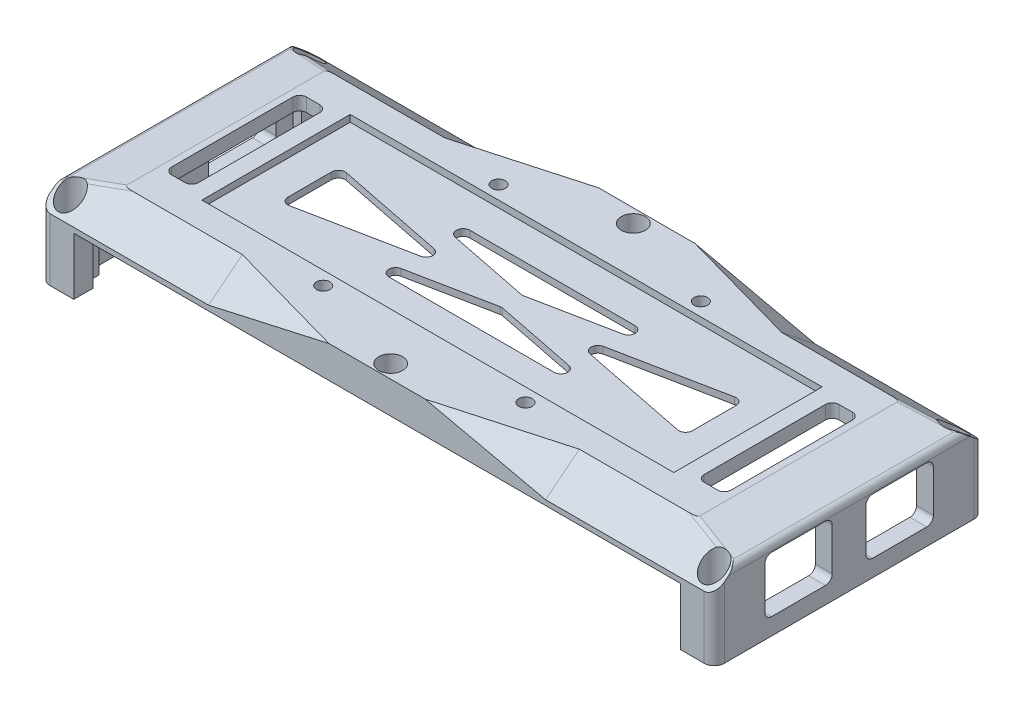
SolidWorks part; units mm, degrees
material "ABS"
ref_plane "前基準面" through (0, 0, 0) normal (0, 0, 1) x (1, 0, 0)
ref_plane "上基準面" through (0, 0, 0) normal (0, 1, 0) x (1, 0, 0)
ref_plane "右基準面" through (0, 0, 0) normal (1, 0, 0) x (0, 0, -1)
sketch "草圖1" plane through (0, 0, 0) normal (0, 1, 0) x (1, 0, 0)
  line L1 (-100, -40) -> (100, -40)
  line L2 (-100, -40) -> (-100, 40)
  line L3 (-100, 40) -> (100, 40)
  line L4 (100, -40) -> (100, -20)
  line L5 (-100, -40) -> (100, 40) construction
  line L6 (-100, 40) -> (100, -40) construction
  line L10 (-1000, 0) -> (49000, 0) construction
  line L17 (-85, 40) -> (-100, 40)
  line L18 (-100, 25) -> (-100, 40)
  line L19 (0, -1000) -> (0, 49000) construction
  line L23 (85, 40) -> (100, 40)
  line L24 (100, 25) -> (100, 40)
  line L29 (100, -25) -> (100, -40)
  line L30 (85, -40) -> (100, -40)
  line L35 (-85, -40) -> (-100, -40)
  line L36 (-100, -25) -> (-100, -40)
  line L40 (100, 0) -> (100, 40)
  line L48 (100, 0) -> (100, -20)
  line L50 (-90, 30) -> (90, 30)
  line L51 (-90, 30) -> (-90, -30)
  line L52 (-90, -30) -> (90, -30)
  line L53 (90, 30) -> (90, -30)
  point P0 (0, 0)
  dimension "D2" = 200
  dimension "D3" = 80
  dimension "D4" = 10
  dimension "D1" = 10
extrude "填料-伸長2" add sketch "草圖1" along normal blind 2 contours L1 L4 L3 L2 L18 L17 L24 L23 L30 L29 L36 L35 region at (-97.8459, 0, 32.5)
sketch "草圖7" plane through (0, 0, 0) normal (0, -1, 0) x (1, 0, 0)
  line L0 (-1000, 0) -> (-95, 0) construction
  line L1 (0, -1010) -> (0, 48990) construction
  line L3 (-30, -30) -> (30, -30)
  line L16 (0, 0) -> (49000, 0) construction
  line L18 (-100, 40) -> (-30, 40)
  line L19 (-100, 40) -> (-100, -40)
  line L20 (-100, -40) -> (-30, -40)
  line L21 (100, 40) -> (100, -40)
  line L22 (-90, 30) -> (-30, 30)
  line L23 (-90, 30) -> (-90, -30)
  line L24 (-90, -30) -> (-30, -30)
  line L25 (90, 30) -> (90, -30)
  line L33 (-30, 40) -> (30, 40)
  line L34 (-30, 30) -> (30, 30)
  line L35 (-30, -40) -> (30, -40)
  line L36 (30, -30) -> (90, -30)
  line L37 (30, -40) -> (100, -40)
  line L38 (30, 40) -> (100, 40)
  line L39 (30, 30) -> (90, 30)
  dimension "D1" = 180
  dimension "D2" = 10
  dimension "D4" = 10
  dimension "D6" = 60
extrude "填料-伸長5" add sketch "草圖7" along normal blind 3.5
sketch "草圖8" plane through (0, 2, 0) normal (0, 1, 0) x (1, 0, 0)
  line L1 (-100, 40) -> (100, 40)
  line L2 (-100, 40) -> (-100, -40)
  line L3 (-100, -40) -> (100, -40)
  line L4 (100, 40) -> (100, -40)
extrude "填料-伸長6" add sketch "草圖8" along normal blind 4
chamfer "導角4" distance 3 distance2 15 2 edges at (-100, 6, 0) (100, 6, 0) first distance on face at (-100, 1.25, 0) first distance on face at (100, 1.25, 0)
sketch "草圖10" plane through (0, -3.5, 0) normal (0, -1, 0) x (1, 0, 0)
  line L0 (-100, -40) -> (100, -40) construction
  line L1 (-100, 40) -> (-90, 40)
  line L2 (-100, 40) -> (-100, -40)
  line L3 (-100, -40) -> (-90, -40)
  line L4 (-90, 40) -> (-90, -40)
  line L5 (0, 0) -> (0, 67.9588) construction
  line L6 (0, 0) -> (59.8785, 0) construction
  line L7 (100, -40) -> (90, -40)
  line L8 (90, 40) -> (90, -40)
  line L9 (100, 40) -> (90, 40)
  line L10 (100, 40) -> (100, -40)
  line L11 (-100, 40) -> (-100, -40) construction
  dimension "D2" = 10
extrude "填料-伸長7" add sketch "草圖10" along normal blind 17
sketch "草圖9" plane through (0, 0, 0) normal (0, 1, 0) x (1, 0, 0)
  line L0 (-1000, 0) -> (49000, 0) construction
  line L1 (0, -994.7968) -> (0, 49005.2032) construction
  line L2 (85, 40) -> (-85, 40) construction
  line L4 (100, -40) -> (100, 40) construction
  circle A0 centre (95.5, 35.5) radius 2
  circle A1 centre (-95.5, 35.5) radius 2
  circle A2 centre (-95.5, -35.5) radius 2
  circle A3 centre (95.5, -35.5) radius 2
  circle A4 centre (0, 36) radius 2
  circle A5 centre (0, -36) radius 2
  circle A6 centre (30, 26) radius 2
  circle A7 centre (-30, 26) radius 2
  circle A8 centre (30, -26) radius 2
  circle A9 centre (-30, -26) radius 2
  dimension "D1" = 4
  dimension "D4" = 4
  dimension "D5" = 4
  dimension "D2" = 4.5
  dimension "D3" = 4.5
  dimension "D6" = 30
  dimension "D7" = 26
  dimension "D8" = 4
extrude "除料-伸長1" cut sketch "草圖9" against normal through all and the other way through all contours A5 | A4 | A1 | A2 | A0 | A3
sketch "草圖11" plane through (0, 6, 0) normal (0, 1, 0) x (1, 0, 0)
  line L0 (0.0013, 21.2615) -> (0.0013, 0) construction
  line L1 (0.0013, 0) -> (-26.9987, 0) construction
  line L2 (100, -40) -> (100, 40) construction
  line L3 (85, 40) -> (-85, 40) construction
  circle A0 centre (-95.4974, 35.5) radius 3.55
  circle A1 centre (-95.4974, -35.5) radius 3.55
  circle A2 centre (95.5, -35.5) radius 3.55
  circle A3 centre (95.5, 35.5) radius 3.55
  dimension "D1" = 7.1
  dimension "D2" = 4.5
  dimension "D4" = 4.5
extrude "除料-伸長2" cut sketch "草圖11" against normal blind 25 contours A1 | A0 | A3 | A2
fillet "圓角1" radius 3 4 edges at (-100, -8.75, 40) (-100, -8.75, -40) (100, -8.75, -40) (100, -8.75, 40)
sketch "草圖12" plane through (0, 6, 0) normal (0, 1, 0) x (1, 0, 0)
  circle A0 centre (0, 36) radius 3.55
  circle A1 centre (0, -36) radius 3.55
  dimension "D1" = 7.1
extrude "除料-伸長3" cut sketch "草圖12" against normal blind 5
sketch "草圖13" plane through (0, 0, 0) normal (1, 0, 0) x (0, 0, -1)
  line L0 (0, 0) -> (0, -20.0336) construction
  line L2 (-25, 1) -> (-5, 1)
  line L3 (-25, 1) -> (-25, -15.5)
  line L4 (-25, -15.5) -> (-5, -15.5)
  line L5 (-5, 1) -> (-5, -15.5)
  line L6 (37, -20.5) -> (-37, -20.5) construction
  line L7 (-40, -20.5) -> (-40, 3.6) construction
  line L8 (25, 1) -> (25, -15.5)
  line L9 (5, 1) -> (5, -15.5)
  line L10 (25, -15.5) -> (5, -15.5)
  line L11 (25, 1) -> (5, 1)
  dimension "D2" = 5
  dimension "D3" = 15
  dimension "D4" = 10
extrude "除料-伸長4" cut sketch "草圖13" against normal through all both and the other way through all
sketch "草圖14" plane through (0, 6, 0) normal (0, 1, 0) x (1, 0, 0)
  line L0 (0, 0) -> (-46.215, 0) construction
  line L1 (0, 0) -> (0, 32.6806) construction
  line L3 (-70, -22) -> (70, -22)
  line L4 (-70, -22) -> (-70, 22)
  line L5 (-70, 22) -> (70, 22)
  line L6 (70, -22) -> (70, 22)
  line L7 (-70, -22) -> (70, 22) construction
  line L8 (-70, 22) -> (70, -22) construction
  dimension "D1" = 140
  dimension "D2" = 44
extrude "除料-伸長7" cut sketch "草圖14" against normal blind 2
sketch "草圖15" plane through (0, 6, 0) normal (0, 1, 0) x (1, 0, 0)
  line L0 (0, 0) -> (27.6246, 0) construction
  line L1 (-83, 20) -> (-75, 20)
  line L2 (-83, 20) -> (-83, -20)
  line L3 (-83, -20) -> (-75, -20)
  line L4 (-75, 20) -> (-75, -20)
  line L5 (0, 0) -> (0, 35.214) construction
  line L6 (83, -20) -> (75, -20)
  line L7 (75, 20) -> (75, -20)
  line L8 (83, 20) -> (75, 20)
  line L9 (83, 20) -> (83, -20)
  line L10 (70, 22) -> (-70, 22) construction
  line L11 (-44.7029, -12) -> (44.7029, -12)
  line L12 (-60, -8.9406) -> (-60, 8.9406)
  line L13 (-44.7029, 12) -> (44.7029, 12)
  line L14 (60, -8.9406) -> (60, 8.9406)
  line L16 (0, -3.0594) -> (44.7029, -12)
  line L17 (-70, 22) -> (-70, -22) construction
  line L18 (-60, 8.9406) -> (-15.2971, 0)
  line L19 (-44.7029, -12) -> (0, -3.0594)
  line L20 (-44.7029, 12) -> (0, 3.0594)
  line L21 (-60, -8.9406) -> (-15.2971, 0)
  line L28 (15.2971, 0) -> (60, -8.9406)
  line L29 (0, 3.0594) -> (44.7029, 12)
  line L30 (15.2971, 0) -> (60, 8.9406)
  dimension "D1" = 40
  dimension "D2" = 75
  dimension "D3" = 8
  dimension "D4" = 10
  dimension "D5" = 10
extrude "除料-伸長8" cut sketch "草圖15" against normal through all
extrude "除料-伸長9" cut sketch "草圖9<5>" along normal blind 6 contours A7 | A6 | A9 | A8
sketch "草圖9<5>" plane through (0, 0, 0) normal (0, 1, 0) x (1, 0, 0) same geometry as "草圖9"
sketch "草圖17" plane through (100, 0, 0) normal (1, 0, 0) x (0, 0, -1)
  line L0 (-40, -2) -> (-30, 6)
  line L1 (-40, -20.5) -> (-40, 3.6) construction
  line L2 (-37, 6) -> (37, 6) construction
  line L3 (0, 0) -> (0, 16.7246) construction
  line L4 (-30, 6) -> (-40, 6)
  line L5 (-40, 6) -> (-40, -2)
  line L6 (30, 6) -> (40, 6)
  line L7 (40, -2) -> (30, 6)
  line L8 (40, 6) -> (40, -2)
  dimension "D1" = 8
  dimension "D2" = 10
extrude "除料-伸長11" cut sketch "草圖17" against normal blind 90 and the other way through all
mirror "鏡射1" about plane through (0, 0, 0) normal (1, 0, 0) of "除料-伸長11"
chamfer "導角3" distance 7 distance2 40 2 edges at (-10, 2, 35) (-10, 2, -35) first distance on face at (-10, 3.3333, 36.6667) first distance on face at (-10, 3.3333, -36.6667)
chamfer "導角5" distance 40 distance2 7 2 edges at (10, 2, -35) (10, 2, 35) first distance on face at (74.1796, 1.6891, -35.3887) first distance on face at (74.1796, 1.6891, 35.3887)
fillet "圓角2" radius 2 46 edges at (75, 4, 20) (83, 4, 20) (83, 4, -20) (75, 4, -20) (-83, 4, -20) (-83, 4, 20) (-75, 4, 20) (-75, 4, -20) (95, -15.5, 25) (95, -15.5, -5) (95, 1, -5) (95, 1, 25) (95, 1, -25) (95, 1, 5) (95, -15.5, 5) (95, -15.5, -25) (-95, 1, 5) (-95, -15.5, -25) (-95, -15.5, 5) (-95, -15.5, 25) (-95, -15.5, -5) (-95, 1, 25) (-95, 1, -5) (-95, 1, -25) (15.2971, 3, 0) (60, 3, 8.9406) (44.7029, 3, -12) (44.7029, 3, 12) (-44.7029, 3, 12) (-44.7029, 3, -12) (0, 3, -3.0594) (-60, 3, 8.9406) (60, 3, -8.9406) (0, 3, 3.0594) (-15.2971, 3, 0) (-60, 3, -8.9406) (-99.1519, 3.1696, -33.538) (-89.5221, 5.0956, -31.1305) (-99.1519, 3.1696, 33.538) (-89.5221, 5.0956, 31.1305) (-100, 3, 0) (99.1535, 3.1693, -33.5384) (89.5229, 5.0954, -31.1307) (99.1535, 3.1693, 33.5384) (89.5229, 5.0954, 31.1307) (100, 3, 0)
sketch "草圖18" plane through (0, 0, 0) normal (1, 0, 0) x (0, 0, -1)
  line L0 (0, 0) -> (0, -34.442) construction
  line L1 (37, -20.5) -> (-37, -20.5) construction
  line L2 (-34.3, -20.5) -> (-5.3, -20.5)
  line L3 (-34.3, -20.5) -> (-34.3, -7)
  line L4 (-34.3, -7) -> (-5.3, -7)
  line L5 (-5.3, -20.5) -> (-5.3, -7)
  line L6 (34.3, -7) -> (5.3, -7)
  line L7 (5.3, -20.5) -> (5.3, -7)
  line L8 (34.3, -20.5) -> (5.3, -20.5)
  line L9 (34.3, -20.5) -> (34.3, -7)
  line L10 (-40, -20.5) -> (-40, -2) construction
  dimension "D1" = 13.5
  dimension "D2" = 5.7
  dimension "D3" = 29
extrude "除料-伸長12" cut sketch "草圖18" against normal mid plane 185
sketch "草圖19" plane through (0, -20.5, 0) normal (0, -1, 0) x (1, 0, 0)
  line L1 (-90, 30) -> (-95, 30)
  line L2 (-90, 30) -> (-90, -30)
  line L3 (-90, -30) -> (-95, -30)
  line L4 (-95, 30) -> (-95, -30)
  line L5 (0, -57.1205) -> (0, 57.1205) construction
  line L6 (0, 0) -> (-76.5655, 0) construction
  line L7 (90, -30) -> (95, -30)
  line L8 (95, 30) -> (95, -30)
  line L9 (90, 30) -> (95, 30)
  line L10 (90, 30) -> (90, -30)
  line L11 (-100, 37) -> (-100, -37) construction
  point P10 (0, 0)
  dimension "D1" = 5
extrude "除料-伸長13" cut sketch "草圖19" against normal blind 22.5
